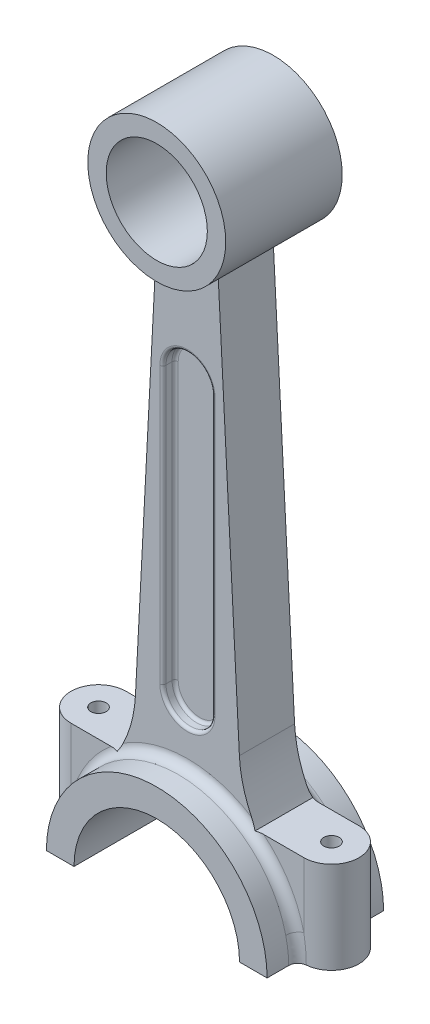
SolidWorks part; units mm, degrees
material "Ductile Iron"
ref_plane "Front Plane" through (0, 0, 0) normal (0, 0, 1) x (1, 0, 0)
ref_plane "Top Plane" through (0, 0, 0) normal (0, 1, 0) x (1, 0, 0)
ref_plane "Right Plane" through (0, 0, 0) normal (1, 0, 0) x (0, 0, -1)
sketch "Sketch3" plane through (0, 0, 0) normal (0, 0, 1) x (1, 0, 0)
  line L0 (0, 0) -> (0.0001, -201.2) construction
  line L1 (-10, -20.1557) -> (-17.8496, -169.9368)
  line L2 (10, -20.1556) -> (17.8498, -169.9368)
  circle A0 centre (0, 0) radius 22.5
  circle A1 centre (0, 0) radius 16.5
  circle A2 centre (0.0001, -201.2) radius 27
  circle A3 centre (0.0001, -201.2) radius 36
  dimension "D1" = 33
  dimension "D2" = 45
  dimension "D3" = 36
  dimension "D4" = 54
  dimension "D5" = 201.2
  dimension "D6" = 20
  dimension "D7" = 6
  dimension "D8" = 149.7811
extrude "Boss-Extrude7" add sketch "Sketch3" along normal mid plane 38 contours A3 A2 | A1 A0 region at (-11.5231, 18.5805, 0) region at (0.0001, -166.2182, 0)
extrude "Boss-Extrude8" add sketch "Sketch3<11>" along normal mid plane 18 contours L0 A0 L1 A3 | A0 L0 A3 L2 region at (7.1844, -100.8455, 0) region at (-7.1843, -100.8455, 0)
sketch "Sketch3<11>" plane through (0, 0, 0) normal (0, 0, 1) x (1, 0, 0) same geometry as "Sketch3"
sketch "Sketch5" plane through (0, 0, 9) normal (0, 0, 1) x (1, 0, 0)
  line L0 (0, 0) -> (0.0001, -201.2) construction
  line L1 (0, -55.6) -> (0.0001, -145.6) construction
  line L2 (8, -55.6) -> (8.0001, -145.6)
  line L3 (-8, -55.6) -> (-7.9999, -145.6)
  arc A0 (8, -55.6) -> (-8, -55.6) centre (0, -55.6) ccw
  arc A1 (-7.9999, -145.6) -> (8.0001, -145.6) centre (0.0001, -145.6) ccw
  point P6 (0.0001, -100.6)
  point P12 (0.0001, -100.6)
  dimension "D2" = 8
  dimension "D1" = 90
extrude "Cut-Extrude7" cut sketch "Sketch5" against normal blind 4 and the other way through all
mirror "Mirror2" about plane through (0, 0, 0) normal (0, 0, 1) of "Cut-Extrude7"
fillet "Fillet1" radius 1 8 edges at (0, -47.6, 5) (8.0001, -100.6, 5) (8.0001, -100.6, 9) (0.0001, -153.6, 5) (0.0001, -153.6, 9) (-7.9999, -100.6, 9) (-7.9999, -100.6, 5) (0, -47.6, 9)
fillet "Fillet2" radius 1 8 edges at (0, -47.6, -9) (8.0001, -100.6, -9) (0.0001, -153.6, -9) (-7.9999, -100.6, -9) (-7.9999, -100.6, -5) (0.0001, -153.6, -5) (8.0001, -100.6, -5) (0, -47.6, -5)
fillet "Fillet8" radius 40 1 edges at (-17.8496, -169.9368, 0)
fillet "Fillet9" radius 40 1 edges at (17.8498, -169.9368, 0)
sketch "Sketch7" plane through (0, 0, -19) normal (0, 0, -1) x (-1, 0, 0)
  line L1 (-44.745, -201.2) -> (39.8152, -201.2)
  line L2 (-44.745, -201.2) -> (-44.745, -245.9452)
  line L3 (-44.745, -245.9452) -> (39.8152, -245.9452)
  line L4 (39.8152, -201.2) -> (39.8152, -245.9452)
extrude "Cut-Extrude11" cut sketch "Sketch7" against normal through all
ref_plane "Plane1" through (0, -171.2, 0) normal (0, -1, 0) x (-1, 0, 0)
sketch "Sketch8" plane through (0, -171.2, 0) normal (0, -1, 0) x (-1, 0, 0)
  line L0 (-38, 0) -> (38, 0) construction
  line L1 (-38, 9) -> (38, 9)
  line L2 (-38, -9) -> (38, -9)
  arc A0 (-38, 9) -> (-38, -9) centre (-38, 0) ccw
  arc A1 (38, -9) -> (38, 9) centre (38, 0) ccw
  point P3 (0, 0)
  dimension "D2" = 9
  dimension "D1" = 76
extrude "Boss-Extrude11" add sketch "Sketch8" along normal up to vertex (30 mm away) up to point (-35.9999, -201.2, -19)
sketch "Sketch9" plane through (0, 0, -9) normal (0, 0, -1) x (-1, 0, 0)
  line L1 (-27.0001, -201.2) -> (26.9999, -201.2)
  line L2 (-27.0001, -201.2) -> (26.9999, -201.2)
  arc A1 (26.9999, -201.2) -> (-27.0001, -201.2) centre (-0.0001, -201.2) ccw
  arc A2 (26.9999, -201.2) -> (-27.0001, -201.2) centre (-0.0001, -201.2) ccw
  dimension "D1" = 0
extrude "Cut-Extrude12" cut sketch "Sketch9" against normal through all
fillet "Fillet20" radius 3 2 edges at (0.0001, -165.2, -9) (0.0001, -165.2, 9)
sketch "Sketch10" plane through (0, -201.2, 0) normal (0, -1, 0) x (1, 0, 0)
  circle A0 centre (-38, 0) radius 2.5
  circle A1 centre (38, 0) radius 2.5
  dimension "D1" = 5
extrude "Cut-Extrude13" cut sketch "Sketch10" against normal through all
